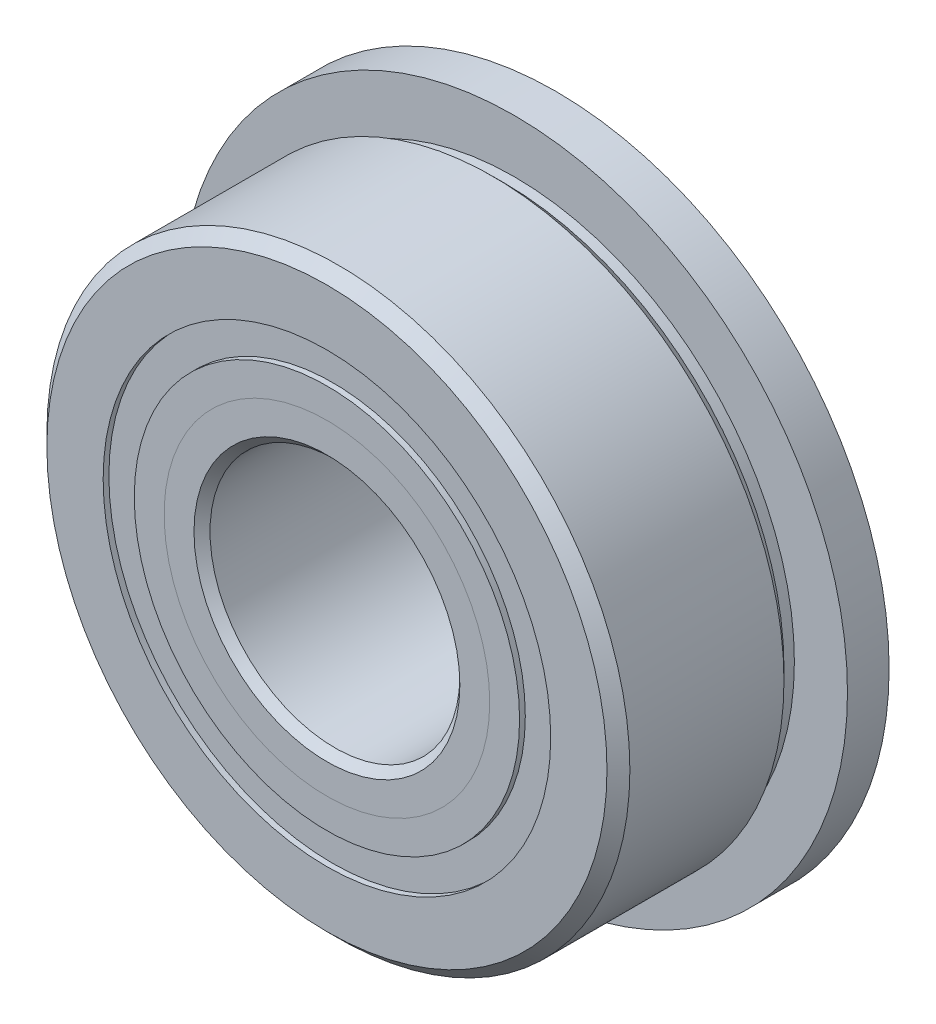
SolidWorks part; units mm, degrees
ref_plane "Front Plane" through (0, 0, 0) normal (0, 0, 1) x (1, 0, 0)
ref_plane "Top Plane" through (0, 0, 0) normal (0, 1, 0) x (1, 0, 0)
ref_plane "Right Plane" through (0, 0, 0) normal (1, 0, 0) x (0, 0, -1)
sketch "Sketch1" plane through (0, 0, 0) normal (1, 0, 0) x (0, 0, -1)
  line L0 (-4.3656, 0) -> (4.3656, 0) construction
  line L1 (0, 11.1125) -> (0, -11.1125) construction
  line L2 (3.9291, 11.1125) -> (-3.9291, 11.1125)
  line L3 (-3.9291, 11.1125) -> (-4.3656, 10.6759)
  line L4 (-4.3656, 10.6759) -> (-4.3656, 8.5306)
  line L5 (-4.3656, 8.5306) -> (-2.4946, 8.5306)
  line L6 (4.3656, 8.5306) -> (2.4946, 8.5306)
  line L7 (4.3656, 10.6759) -> (4.3656, 8.5306)
  line L8 (3.9291, 11.1125) -> (4.3656, 10.6759)
  line L9 (0, 11.1125) -> (0, 7.9375) construction
  line L10 (0, 7.9375) -> (0, 4.7625) construction
  line L11 (4.3656, 0) -> (5.9531, 0) construction
  arc A0 (-2.4946, 8.5306) -> (2.4946, 8.5306) centre (0, 7.9375) cw
  point P14 (0, 4.7625)
  dimension "OD" = 22.225
  dimension "D1" = 45
  dimension "D2" = 0.4366
  dimension "Shaft Dia" = 9.525
  dimension "D3" = 4.9893
  dimension "D4" = 0.5931
  dimension "Width" = 8.7312
  dimension "Total Wd" = 10.3187
revolve "Revolve1" add sketch "Sketch1" angle 360 about L0
sketch "Sketch2" plane through (0, 0, 0) normal (1, 0, 0) x (0, 0, -1)
  line L0 (-4.3656, 7.3444) -> (-2.4946, 7.3444)
  line L1 (-4.3656, 10.6759) -> (-4.3656, -10.6759) construction
  line L2 (-4.3656, 7.3444) -> (-4.3656, 6.2061)
  line L3 (-4.3656, 6.2061) -> (-3.2274, 5.0679)
  line L4 (-3.2274, 5.0679) -> (0, 5.0679)
  line L5 (0, 11.1125) -> (0, -11.1125) construction
  line L6 (0, 5.0679) -> (0, 5.3733)
  line L7 (0, 5.3733) -> (0, 4.7625) construction
  line L8 (-4.3656, 7.3444) -> (-4.3656, 5.0679) construction
  line L9 (-4.3656, 5.0679) -> (-3.2274, 5.0679) construction
  arc A0 (-2.4946, 7.3444) -> (0, 5.3733) centre (0, 7.9375) ccw
  arc A1 (2.4946, 8.5306) -> (-2.4946, 8.5306) centre (0, 7.9375) ccw construction
  circle A2 centre (0, 7.9375) radius 2.5642 construction
  dimension "D1" = 45
revolve "Revolve2" add sketch "Sketch2" angle 360 about L0
sketch "Sketch3" plane through (0, 0, 0) normal (1, 0, 0) x (0, 0, -1)
  line L0 (-4.3656, 6.2061) -> (-3.2274, 5.0679)
  line L1 (-3.2274, 5.0679) -> (0, 5.0679)
  line L2 (0, 5.0679) -> (0, 5.3733)
  line L3 (-4.3656, 6.2061) -> (-4.3656, 5.0679)
  line L4 (-4.3656, 7.3444) -> (-4.3656, 5.0679) construction
  line L5 (-4.3656, 5.0679) -> (-4.0602, 4.7625)
  line L6 (-4.0602, 4.7625) -> (5.5166, 4.7625)
  line L7 (10.4392, 0) -> (-10.4392, 0) construction
  line L8 (5.5166, 4.7625) -> (5.9531, 5.1991)
  line L10 (5.9531, 5.1991) -> (5.9531, 5.9563)
  line L11 (5.9531, 5.9563) -> (1.6278, 5.9563)
  line L13 (3.9291, 11.1125) -> (4.3656, 10.6759) construction
  circle A0 centre (0, 7.9375) radius 2.5642 construction
  arc A1 (1.6278, 5.9563) -> (0, 5.3733) centre (0, 7.9375) cw
  point P18 (0, 0)
  dimension "Inner Ring OD" = 11.9126
revolve "Revolve3" add sketch "Sketch3" angle 360 about L0
sketch "Sketch5" plane through (0, 0, 0) normal (1, 0, 0) x (0, 0, -1)
  line L0 (4.3656, 10.6759) -> (4.3656, 8.5306) construction
  line L1 (4.3656, 9.6033) -> (2.7781, 9.6033)
  line L2 (4.3656, 9.6033) -> (4.3656, 12.7)
  line L3 (4.3656, 12.7) -> (2.7781, 12.7)
  line L4 (2.7781, 9.6033) -> (2.7781, 12.7)
  line L5 (5.9531, 0) -> (-4.3656, 0) construction
  dimension "D1" = 1.5875
  dimension "Flange OD" = 25.4
revolve "Revolve5" add sketch "Sketch5" angle 360 about L5
sketch "Sketch6" plane through (0, 0, 0) normal (1, 0, 0) x (0, 0, -1)
  line L0 (1.9447, 11.1125) -> (2.3813, 10.6759)
  line L1 (3.9291, 11.1125) -> (-3.9291, 11.1125) construction
  line L2 (2.3813, 10.6759) -> (2.7781, 10.6759)
  line L3 (2.7781, 10.6759) -> (2.7781, 11.1125)
  line L4 (2.7781, 11.1125) -> (1.9447, 11.1125)
  line L5 (3.9291, 11.1125) -> (4.3656, 10.6759) construction
  line L6 (2.7781, 9.6033) -> (2.7781, 12.7) construction
  dimension "D1" = 0.3969
revolve "Cut-Revolve1" cut sketch "Sketch6" angle 360 about L0
sketch "Sketch4" plane through (0, 0, 0) normal (1, 0, 0) x (0, 0, -1)
  line L0 (-2.5642, 7.9375) -> (2.5642, 7.9375)
  circle A1 centre (0, 7.9375) radius 2.5642 construction
  arc A2 (-2.5642, 7.9375) -> (2.5642, 7.9375) centre (0, 7.9375) cw
  arc A3 (2.4946, 8.5306) -> (-2.4946, 8.5306) centre (0, 7.9375) ccw construction
revolve "Revolve4" add sketch "Sketch4" angle 360 about L0
ref_axis "Axis1" through (0, 0, -4.3656) along (0, 0, 1)
pattern_circular "CirPattern1" count 12 every 30 about axis through (0, 0, -4.3656) along (0, 0, 1) of bodies 104
sketch "Sketch7" plane through (0, 0, 0) normal (1, 0, 0) x (0, 0, -1)
  line L0 (-4.3656, 8.5306) -> (-2.4946, 8.5306) construction
  line L1 (-4.1473, 8.5306) -> (-2.5642, 8.5306)
  line L2 (-4.1473, 8.5306) -> (-4.1473, 7.3444)
  line L3 (-4.1473, 7.3444) -> (-2.5642, 7.3444)
  line L4 (-2.5642, 8.5306) -> (-2.5642, 7.3444)
  line L5 (-4.3656, 7.3444) -> (-2.4946, 7.3444) construction
  line L6 (-3.9291, 11.1125) -> (-4.3656, 10.6759) construction
  line L7 (4.3656, 8.5306) -> (2.4946, 8.5306) construction
  line L8 (4.1473, 8.5306) -> (2.5642, 8.5306)
  line L9 (4.1473, 8.5306) -> (4.1473, 5.9563)
  line L10 (4.1473, 5.9563) -> (2.5642, 5.9563)
  line L11 (2.5642, 8.5306) -> (2.5642, 5.9563)
  line L12 (5.9531, 5.9563) -> (1.6278, 5.9563) construction
  line L13 (3.9291, 11.1125) -> (4.3656, 10.6759) construction
  circle A0 centre (0, 7.9375) radius 2.5642 construction
  point P10 (-4.1473, 10.8942)
  point P21 (4.1473, 10.8942)
revolve "Revolve6" add sketch "Sketch7" angle 360 about L0
equation "\"D2@Sketch1\" = \"Width@Sketch1\"*.05"
equation "\"D3@Sketch1\"=\"Width@Sketch1\"/1.75"
equation "\"D4@Sketch1\" = (((\"OD@Sketch1\"-\"Width@Sketch1\")/2)/3.25)/3.5"
equation "\"D2@CirPattern1\" = 360/\"Balls@CirPattern1\""
